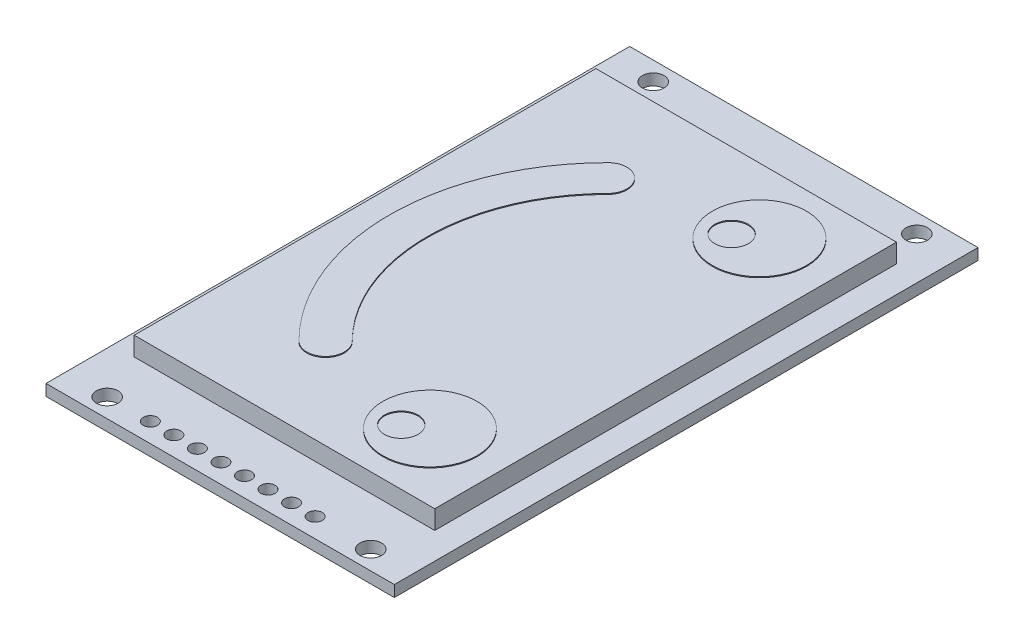
SolidWorks part; units mm, degrees
ref_plane "Front Plane" through (0, 0, 0) normal (0, 0, 1) x (1, 0, 0)
ref_plane "Top Plane" through (0, 0, 0) normal (0, 1, 0) x (1, 0, 0)
ref_plane "Right Plane" through (0, 0, 0) normal (1, 0, 0) x (0, 0, -1)
sketch "Sketch1" plane through (0, 0, 0) normal (0, 1, 0) x (1, 0, 0)
  line L0 (32.5, 60) -> (32.5, 2) construction
  line L1 (0, 0) -> (37, 0)
  line L2 (0, 0) -> (0, 62)
  line L3 (0, 62) -> (37, 62)
  line L4 (37, 0) -> (37, 62)
  line L5 (32.5, 2) -> (4.5, 2) construction
  line L6 (4.5, 2) -> (4.5, 60) construction
  line L7 (4.5, 60) -> (32.5, 60) construction
  line L8 (18.5, 2) -> (18.5, 0) construction
  line L9 (4.5, 31) -> (0, 31) construction
  circle A0 centre (32.5, 60) radius 1.15
  circle A1 centre (4.5, 60) radius 1.15
  circle A2 centre (32.5, 2) radius 1.15
  circle A3 centre (4.5, 2) radius 1.15
  dimension "D3" = 2.3
  dimension "D1" = 37
  dimension "D2" = 62
  dimension "D4" = 28
  dimension "D5" = 58
extrude "Boss-Extrude1" add sketch "Sketch1" along normal blind 1.2
sketch "Sketch2" plane through (0, 1.2, 0) normal (0, 1, 0) x (1, 0, 0)
  line L1 (2.2462, 56.1674) -> (34.1749, 56.1674)
  line L2 (2.2462, 56.1674) -> (2.2462, 7.1205)
  line L3 (2.2462, 7.1205) -> (34.1749, 7.1205)
  line L4 (34.1749, 56.1674) -> (34.1749, 7.1205)
extrude "Boss-Extrude2" add sketch "Sketch2" along normal blind 2
sketch "Sketch3" plane through (0, 1.2, 0) normal (0, 1, 0) x (1, 0, 0)
  circle A0 centre (9.0316, 2.0507) radius 0.75
  circle A1 centre (11.5316, 2.0507) radius 0.75
  circle A2 centre (14.0316, 2.0507) radius 0.75
  circle A3 centre (16.5316, 2.0507) radius 0.75
  circle A4 centre (19.0316, 2.0507) radius 0.75
  circle A5 centre (21.5316, 2.0507) radius 0.75
  circle A6 centre (24.0316, 2.0507) radius 0.75
  circle A7 centre (26.5316, 2.0507) radius 0.75
  dimension "D1" = 1.5
  dimension "D2" = 8
extrude "Cut-Extrude1" cut sketch "Sketch3" against normal through all
sketch "Sketch4" plane through (0, 3.2, 0) normal (0, 1, 0) x (1, 0, 0)
  line L0 (26.6399, 49.1439) -> (26.6399, 14.1439) construction
  line L1 (13.0544, 46.6439) -> (13.0544, 16.6439) construction
  line L2 (26.6399, 31.6439) -> (13.0544, 31.6439) construction
  line L3 (34.1749, 31.6439) -> (26.6399, 31.6439) construction
  line L4 (34.1749, 7.1205) -> (34.1749, 56.1674) construction
  circle A0 centre (26.6399, 49.1439) radius 5
  circle A1 centre (26.6399, 14.1439) radius 5
  arc A2 (11.6401, 48.0582) -> (11.6401, 15.2297) centre (28.0544, 31.6439) ccw
  arc A3 (14.4686, 45.2297) -> (14.4686, 18.0582) centre (28.0544, 31.6439) ccw
  arc A4 (14.4686, 45.2297) -> (11.6401, 48.0582) centre (13.0544, 46.6439) ccw
  arc A5 (14.4686, 18.0582) -> (11.6401, 15.2297) centre (13.0544, 16.6439) cw
  circle A6 centre (24.7633, 12.9717) radius 1.7861
  circle A7 centre (24.7633, 48.0582) radius 1.7861
  dimension "D1" = 35
  dimension "D2" = 10
  dimension "D4" = 2
  dimension "D3" = 30
  dimension "D5" = 15
extrude "Boss-Extrude3" add sketch "Sketch4" along normal blind 0.1
ref_plane "Plane1" through (0, 0, -31.6439) normal (0, 0, 1) x (1, 0, 0)
